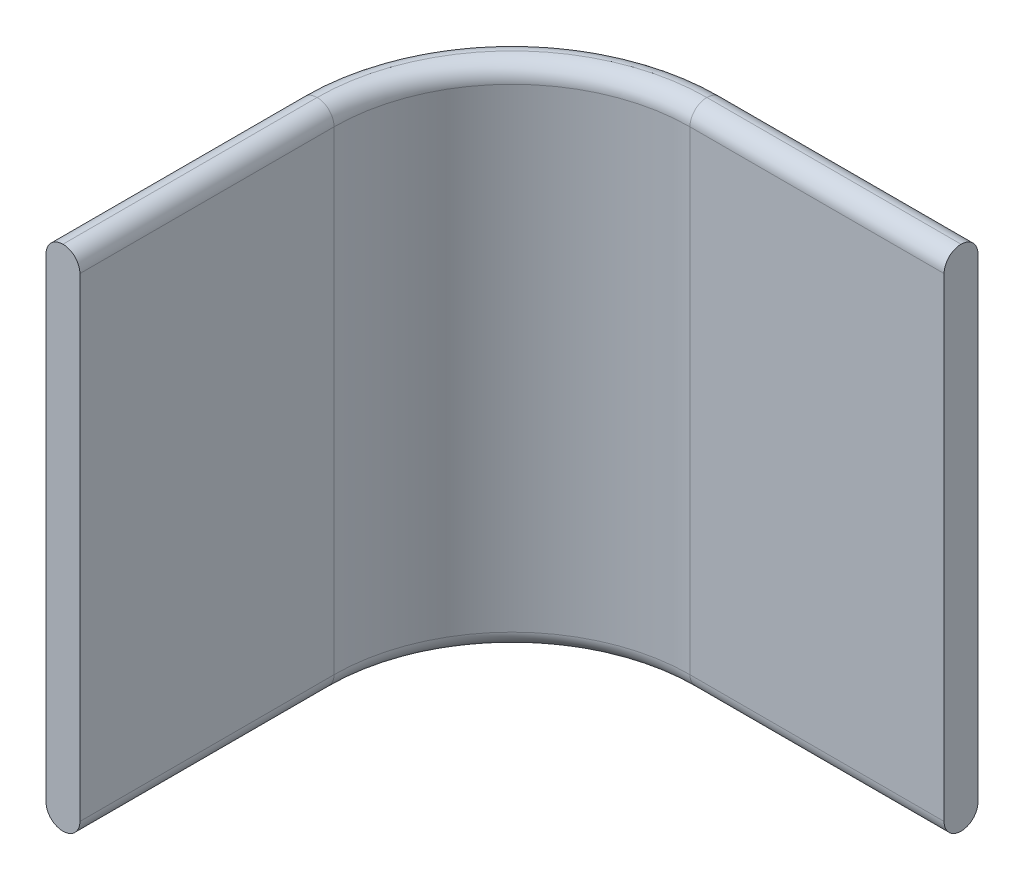
SolidWorks part; units mm, degrees
ref_plane "Front Plane" through (0, 0, 0) normal (0, 0, 1) x (1, 0, 0)
ref_plane "Top Plane" through (0, 0, 0) normal (0, 1, 0) x (1, 0, 0)
ref_plane "Right Plane" through (0, 0, 0) normal (1, 0, 0) x (0, 0, -1)
sketch "Sketch1" plane through (0, 0, 0) normal (0, 1, 0) x (1, 0, 0)
  line L0 (-25, 0) -> (-25, -15)
  line L1 (-25, -15) -> (-21, -15) construction
  line L2 (-21, -15) -> (-21, 0)
  line L3 (0.2522, -0.2522) -> (-18603.6661, 18603.6661) construction
  line L4 (15, 21) -> (0, 21)
  line L5 (15, 25) -> (15, 21) construction
  line L6 (0, 25) -> (15, 25)
  line L7 (-25, -15) -> (-25, -30)
  line L8 (-25, -30) -> (-21, -30)
  line L9 (-21, -30) -> (-21, -15)
  line L10 (15, 21) -> (30, 21)
  line L11 (30, 21) -> (30, 25)
  line L12 (30, 25) -> (15, 25)
  arc A0 (0, 25) -> (-25, 0) centre (0, 0) ccw
  arc A1 (0, 21) -> (-21, 0) centre (0, 0) ccw
  point P11 (-14.8492, 14.8492)
  dimension "D1" = 4
  dimension "D2" = 40
  dimension "D3" = 15
extrude "Boss-Extrude1" add sketch "Sketch1" along normal blind 60
fillet "Fillet1" radius 2 12 edges at (15, 0, -25) (-25, 0, 15) (-21, 0, 15) (15, 0, -21) (15, 60, -25) (-25, 60, 15) (-21, 60, 15) (15, 60, -21) (-17.6777, 0, -17.6777) (-14.8492, 0, -14.8492) (-17.6777, 60, -17.6777) (-14.8492, 60, -14.8492)
